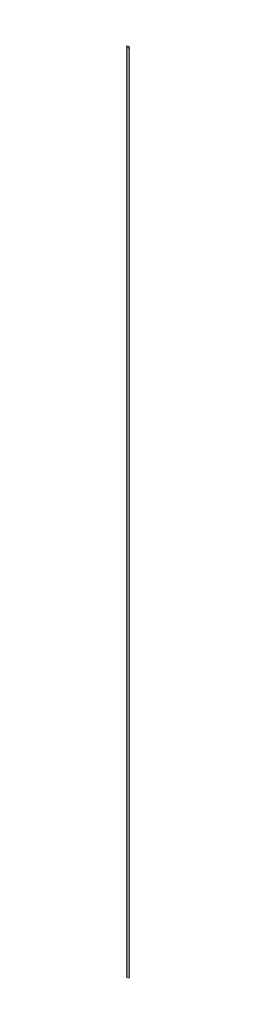
SolidWorks part; units mm, degrees
ref_plane "Front Plane" through (0, 0, 0) normal (0, 0, 1) x (1, 0, 0)
ref_plane "Top Plane" through (0, 0, 0) normal (0, 1, 0) x (1, 0, 0)
ref_plane "Right Plane" through (0, 0, 0) normal (1, 0, 0) x (0, 0, -1)
sketch "Sketch1" plane through (0, 0, 0) normal (0, 1, 0) x (1, 0, 0)
  line L0 (0, 0) -> (38.1, 0) construction
  line L1 (0, 31.75) -> (38.1, 31.75)
  line L2 (0, -31.75) -> (38.1, -31.75)
  line L3 (0, 0) -> (38.1, 0) construction
  line L4 (0, 20.3048) -> (38.1, 20.3048)
  line L5 (0, -20.3048) -> (38.1, -20.3048)
  arc A0 (0, 31.75) -> (0, -31.75) centre (0, 0) ccw
  arc A1 (38.1, -31.75) -> (38.1, 31.75) centre (38.1, 0) ccw
  arc A2 (0, 20.3048) -> (0, -20.3048) centre (0, 0) ccw
  arc A3 (38.1, -20.3048) -> (38.1, 20.3048) centre (38.1, 0) ccw
  point P3 (19.05, 0)
  point P10 (19.05, 0)
  dimension "D1" = 38.1
  dimension "D2" = 63.5
sketch "Sketch2" plane through (0, 0, 0) normal (1, 0, 0) x (0, 0, -1)
  line L0 (0, 0) -> (0, 30378.4)
  dimension "D1" = 30378.4
sweep "Sweep1" add profiles "Sketch1" path "Sketch2"
sketch "Sketch3" plane through (0, 30378.4, 0) normal (0, 1, 0) x (1, 0, 0)
  line L0 (19.05, 20.3048) -> (19.05, -20.3048) construction
  line L1 (0, 20.3048) -> (38.1, 20.3048) construction
  line L2 (38.1, -20.3048) -> (0, -20.3048) construction
  line L3 (-20.3048, 0) -> (58.4048, 0) construction
  arc A0 (0, 20.3048) -> (0, -20.3048) centre (0, 0) ccw construction
  arc A1 (38.1, -20.3048) -> (38.1, 20.3048) centre (38.1, 0) ccw construction
sketch "Sketch4" plane through (0, 0, 0) normal (0, -1, 0) x (1, 0, 0)
  line L0 (19.05, 20.3048) -> (19.05, -20.3048) construction
  line L1 (-20.3048, 0) -> (58.4048, 0) construction
